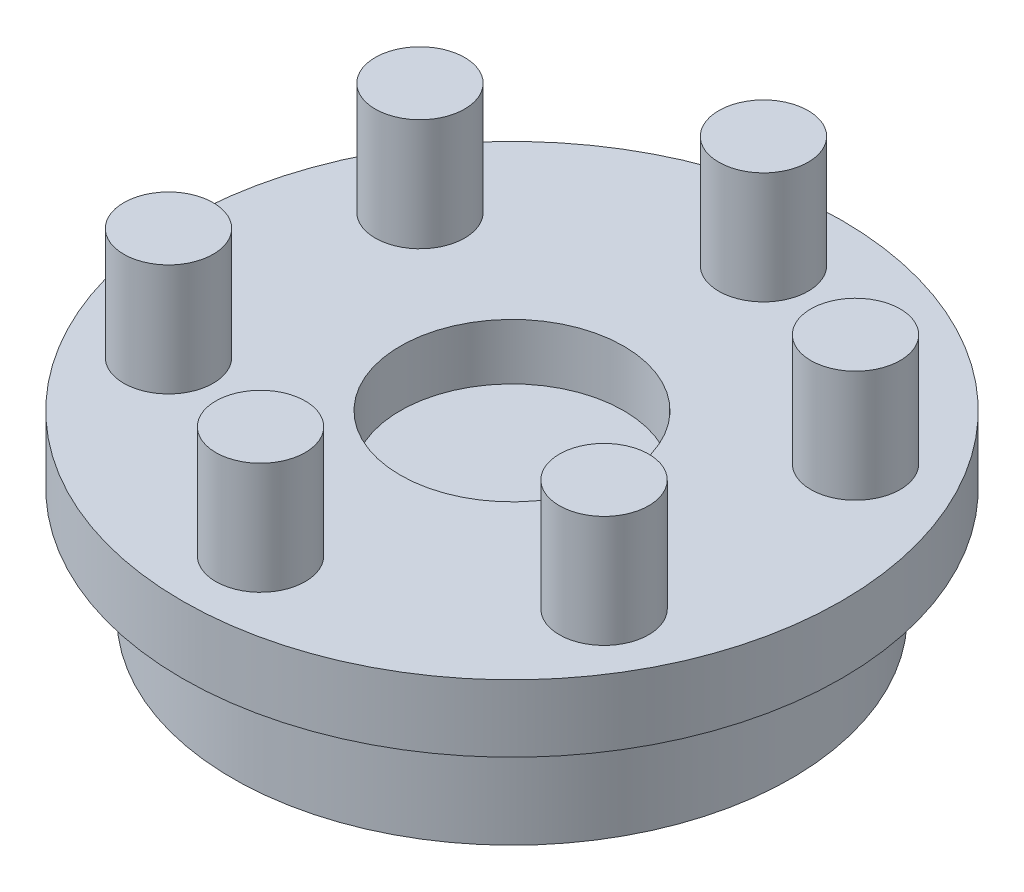
SolidWorks part; units mm, degrees
material "6061-T6 (SS)"
ref_plane "Front Plane" through (0, 0, 0) normal (0, 0, 1) x (1, 0, 0)
ref_plane "Top Plane" through (0, 0, 0) normal (0, 1, 0) x (1, 0, 0)
ref_plane "Right Plane" through (0, 0, 0) normal (1, 0, 0) x (0, 0, -1)
sketch "Sketch1" plane through (0, 0, 0) normal (0, 1, 0) x (1, 0, 0)
  circle A0 centre (0, 0) radius 29.5
  circle A1 centre (0, 0) radius 22.5 construction
  circle A2 centre (0, 22.5) radius 4
  circle A3 centre (19.4856, 11.25) radius 4
  circle A4 centre (19.4856, -11.25) radius 4
  circle A5 centre (0, -22.5) radius 4
  circle A6 centre (-19.4856, -11.25) radius 4
  circle A7 centre (-19.4856, 11.25) radius 4
  circle A8 centre (0, 0) radius 10
  point P18 (0, 0)
  dimension "D1" = 45
  dimension "D2" = 59
  dimension "D3" = 8
  dimension "D5" = 20
  dimension "D4" = 6
extrude "Boss-Extrude1" add sketch "Sketch1" along normal blind 10 contours A2 | A7 | A6 | A5 | A4 | A3
extrude "Boss-Extrude2" add sketch "Sketch1<4>" against normal blind 6 separate body contours A0 A8 A7 A6 A5 A4 A3 A2 | A7 | A6 | A5 | A4 | A3 | A2 | A7 | A6 | A5 | A4 | A3 | A2 | A0 region at (-28.6656, 0, 0) region at (0, 0, -22.5) region at (19.4856, 0, -11.25) region at (19.4856, 0, 11.25) region at (0, 0, 22.5) region at (-19.4856, 0, 11.25) region at (-19.4856, 0, -11.25)
sketch "Sketch1<4>" plane through (0, 0, 0) normal (0, 1, 0) x (1, 0, 0) same geometry as "Sketch1"
extrude "Cut-Extrude1" cut sketch "Sketch1<5>" against normal blind 5 contours A8
sketch "Sketch1<5>" plane through (0, 0, 0) normal (0, 1, 0) x (1, 0, 0) same geometry as "Sketch1"
sketch "Sketch2" plane through (0, -6, 0) normal (0, -1, 0) x (1, 0, 0)
  circle A0 centre (0, 0) radius 25
  dimension "D1" = 50
extrude "Boss-Extrude3" add sketch "Sketch2" along normal blind 10
sketch "Sketch3" plane through (0, -16, 0) normal (0, -1, 0) x (1, 0, 0)
  circle A0 centre (0, 0) radius 15
  dimension "D1" = 30
extrude "Cut-Extrude2" cut sketch "Sketch3" against normal blind 8
sketch "Sketch4" plane through (0, -16, 0) normal (0, -1, 0) x (1, 0, 0)
  point P0 (0, 20)
  point P1 (0, 0)
  dimension "D1" = 20
hole_wizard "M5 Tapped Hole1" positions "Sketch5" profile "Sketch6" tap size "M5" standard "ISO"
sketch "Sketch5" plane through (0, -16, 0) normal (0, -1, 0) x (-1, 0, 0)
  point P0 (0, -20)
sketch "Sketch6" plane through (0, -16, 20) normal (1, 0, 0) x (0, 0, -1)
  line L0 (0, 0) -> (0, 9.2618)
  line L1 (0, 9.2618) -> (2.1, 8)
  line L2 (2.1, 8) -> (2.1, 0.425)
  line L3 (2.1, 0.425) -> (2.525, 0)
  line L5 (2.525, 0) -> (0, 0)
  line L6 (-2.1, 0.425) -> (-2.525, 0) construction
  line L10 (0, 9.2618) -> (-2.1, 8) construction
  line L11 (0, -6.35) -> (0, 107.95) construction
  dimension "Tap Drill Dia." = 4.2
  dimension "Tap Drill Depth" = 8
  dimension "Near C'Sink Dia." = 5.05
  dimension "Near C'Sink Angle" = 90
  dimension "Drill Angle" = 118
pattern_circular "CirPattern1" count 8 over 360 about axis through (0, -16, 0) along (0, -1, 0) of "M5 Tapped Hole1"
sketch "Sketch7" plane through (0, -16, 0) normal (0, -1, 0) x (1, 0, 0)
  line L0 (0, 0) -> (-21.2483, -8.8014) construction
  line L1 (-20, 0) -> (0, 0) construction
  arc A8 (-22.712, -3.6222) -> (-18.6211, -13.4985) centre (0, 0) ccw
  arc A9 (-16.7131, -3.11) -> (-14.017, -9.6189) centre (0, 0) ccw
  arc A10 (-22.712, -3.6222) -> (-16.7131, -3.11) centre (-20, 0) ccw
  arc A11 (-14.017, -9.6189) -> (-18.6211, -13.4985) centre (-14.1421, -14.1421) ccw
  point P7 (-15.706, -6.5056)
  point P11 (0, 0)
  dimension "D2" = 10.69
  dimension "D5" = 7.0452
  dimension "D6" = 17
  dimension "D1" = 22.5
extrude "Cut-Extrude3" cut sketch "Sketch7" against normal blind 8
fillet "Fillet1" radius 1 4 edges at (-22.712, -12, -3.6222) (-18.6211, -12, -13.4985) (-14.017, -12, -9.6189) (-16.7131, -12, -3.11)
pattern_circular "CirPattern2" count 8 over 360 about axis through (0, -16, 0) along (0, -1, 0) of "Fillet1", "Cut-Extrude3"
